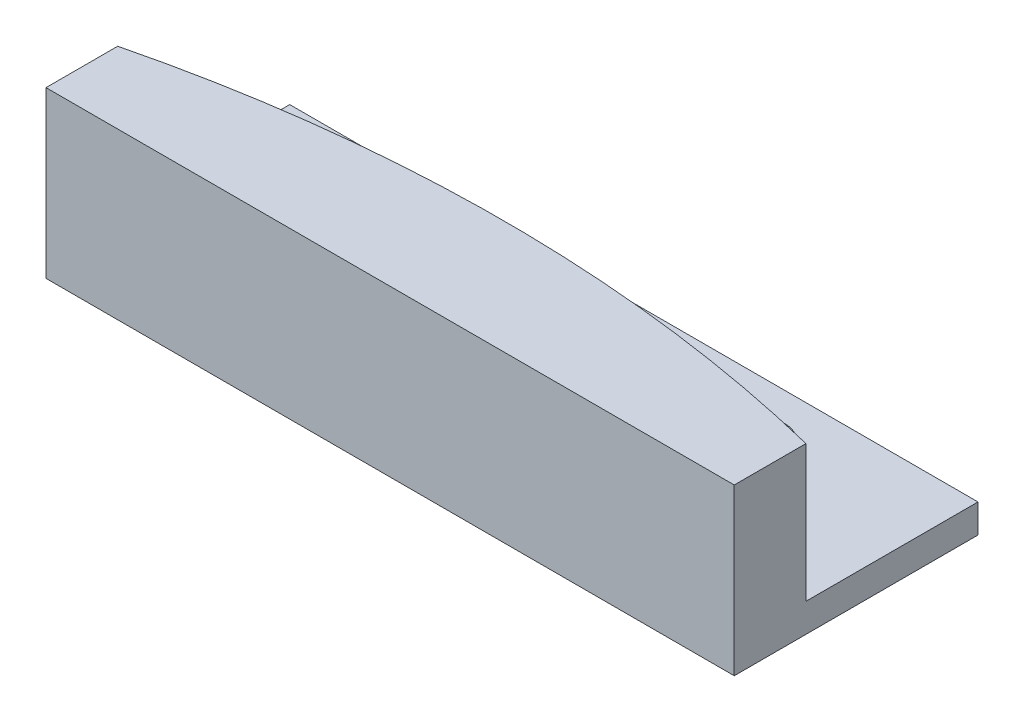
SolidWorks part; units mm, degrees
ref_plane "Front Plane" through (0, 0, 0) normal (0, 0, 1) x (1, 0, 0)
ref_plane "Top Plane" through (0, 0, 0) normal (0, 1, 0) x (1, 0, 0)
ref_plane "Right Plane" through (0, 0, 0) normal (1, 0, 0) x (0, 0, -1)
sketch "Sketch1" plane through (0, 0, 0) normal (0, 1, 0) x (1, 0, 0)
  line L0 (-24, 0) -> (24, 0)
  line L1 (24, 0) -> (24, 5)
  line L2 (-24, 5) -> (-24, 0)
  line L3 (-24, 5) -> (-24, 17)
  line L4 (-24, 17) -> (24, 17)
  line L5 (24, 17) -> (24, 5)
  line L6 (0, 0) -> (0, 22) construction
  circle A0 centre (0, -92.0773) radius 100 construction
  arc A1 (-24, 5) -> (24, 5) centre (0, -92.0773) cw
  circle A2 centre (-12.5, 13) radius 2
  circle A3 centre (12.5, 13) radius 2
  point P6 (0, 0)
  dimension "D2" = 100
  dimension "D3" = 5
  dimension "D7" = 4
  dimension "D1" = 48
  dimension "D4" = 12
  dimension "D5" = 12.5
  dimension "D6" = 4
extrude "Boss-Extrude1" add sketch "Sketch1" along normal blind 11.525 contours A1 L2 L0 L1 region at (0, 0, -3.5315)
extrude "Boss-Extrude2" add sketch "Sketch1<3>" along normal blind 2 contours L3 A1 L5 L4 region at (0, 0, -11.8812)
sketch "Sketch1<3>" plane through (0, 0, 0) normal (0, 1, 0) x (1, 0, 0) same geometry as "Sketch1"
